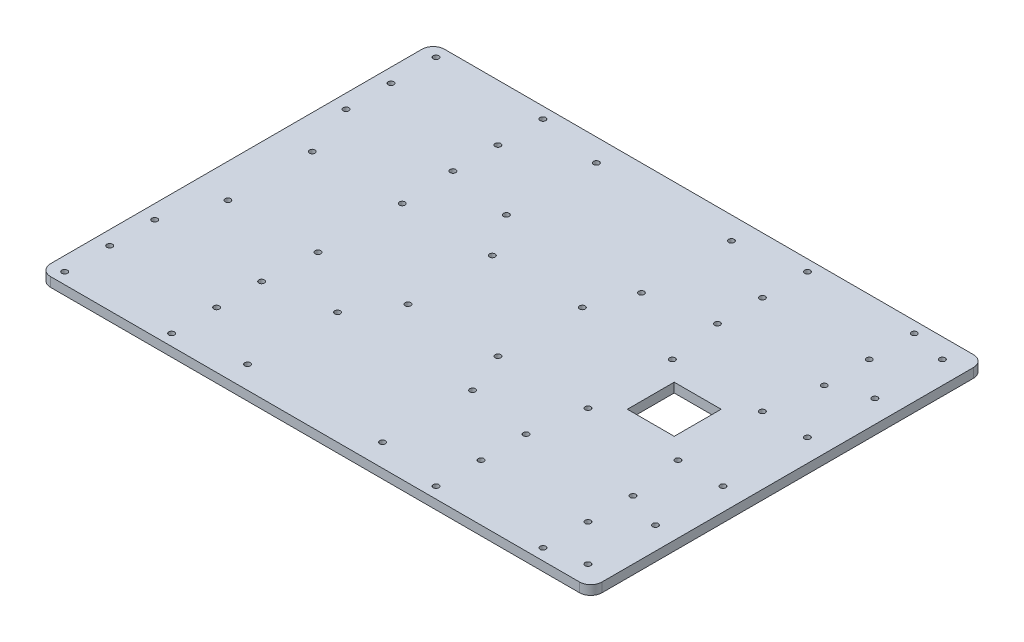
SolidWorks part; units mm, degrees
ref_plane "Front Plane" through (0, 0, 0) normal (0, 0, 1) x (1, 0, 0)
ref_plane "Top Plane" through (0, 0, 0) normal (0, 1, 0) x (1, 0, 0)
ref_plane "Right Plane" through (0, 0, 0) normal (1, 0, 0) x (0, 0, -1)
sketch "Sketch1" plane through (0, 0, 0) normal (0, 1, 0) x (1, 0, 0)
  line L0 (-127.5, 105) -> (-127.5, -105) construction
  line L1 (-129, -105) -> (129, -105)
  line L2 (-135, -99) -> (-135, 99)
  line L3 (-129, 105) -> (129, 105)
  line L4 (135, -99) -> (135, 99) construction
  line L5 (-135, -105) -> (135, 105) construction
  line L6 (-135, 105) -> (135, -105) construction
  line L8 (0, 105) -> (0, -105) construction
  line L9 (-135, 0) -> (135, 0) construction
  line L13 (129, 105) -> (153, 105)
  line L14 (159, 99) -> (159, -99)
  line L15 (153, -105) -> (129, -105)
  line L16 (147, 105) -> (147, -105) construction
  line L17 (159, -22.5) -> (-135, -22.5) construction
  line L19 (86, -12.5) -> (111, -12.5)
  line L20 (86, -12.5) -> (86, 12.5)
  line L21 (86, 12.5) -> (111, 12.5)
  line L22 (111, -12.5) -> (111, 12.5)
  line L23 (86, -12.5) -> (111, 12.5) construction
  line L24 (86, 12.5) -> (111, -12.5) construction
  line L25 (-36, -93) -> (36, -93) construction
  line L26 (-36, -93) -> (-36, -45) construction
  line L27 (-36, -45) -> (36, -45) construction
  line L28 (36, -93) -> (36, -45) construction
  line L29 (-36, -93) -> (36, -45) construction
  line L30 (-36, -45) -> (36, -93) construction
  circle A0 centre (-127.5, 99) radius 1.5
  circle A1 centre (-127.5, 75) radius 1.5
  circle A2 centre (-127.5, 51) radius 1.5
  circle A3 centre (-70.5, 99) radius 1.5
  circle A4 centre (-70.5, 75) radius 1.5
  circle A5 centre (-70.5, 51) radius 1.5
  circle A6 centre (70.5, 51) radius 1.5
  circle A7 centre (70.5, 75) radius 1.5
  circle A8 centre (70.5, 99) radius 1.5
  circle A9 centre (127.5, 51) radius 1.5
  circle A10 centre (127.5, 75) radius 1.5
  circle A11 centre (127.5, 99) radius 1.5
  circle A12 centre (127.5, -99) radius 1.5
  circle A13 centre (127.5, -75) radius 1.5
  circle A14 centre (127.5, -51) radius 1.5
  circle A15 centre (70.5, -99) radius 1.5
  circle A16 centre (70.5, -75) radius 1.5
  circle A17 centre (70.5, -51) radius 1.5
  circle A18 centre (-70.5, -51) radius 1.5
  circle A19 centre (-70.5, -75) radius 1.5
  circle A20 centre (-70.5, -99) radius 1.5
  circle A21 centre (-127.5, -51) radius 1.5
  circle A22 centre (-127.5, -75) radius 1.5
  circle A23 centre (-127.5, -99) radius 1.5
  arc A37 (129, 105) -> (135, 99) centre (129, 99) cw construction
  arc A38 (135, -99) -> (129, -105) centre (129, -99) cw construction
  arc A39 (-129, -105) -> (-135, -99) centre (-129, -99) cw
  arc A40 (-135, 99) -> (-129, 105) centre (-129, 99) cw
  arc A43 (153, -105) -> (159, -99) centre (153, -99) ccw
  arc A44 (159, 99) -> (153, 105) centre (153, 99) ccw
  circle A45 centre (147, -94.5) radius 1.5
  circle A46 centre (147, -58.5) radius 1.5
  circle A47 centre (147, -22.5) radius 1.5
  circle A51 centre (123, -22.5) radius 1.5
  circle A52 centre (75, -22.5) radius 1.5
  circle A53 centre (27, -22.5) radius 1.5
  circle A54 centre (-21, -22.5) radius 1.5
  circle A55 centre (-69, -22.5) radius 1.5
  circle A56 centre (-117, -22.5) radius 1.5
  circle A57 centre (-36, -93) radius 1.5
  circle A58 centre (36, -93) radius 1.5
  circle A59 centre (36, -45) radius 1.5
  circle A60 centre (-36, -45) radius 1.5
  circle A61 centre (123, 22.5) radius 1.5
  circle A62 centre (75, 22.5) radius 1.5
  circle A63 centre (27, 22.5) radius 1.5
  circle A64 centre (-21, 22.5) radius 1.5
  circle A65 centre (-69, 22.5) radius 1.5
  circle A66 centre (-117, 22.5) radius 1.5
  circle A67 centre (36, 93) radius 1.5
  circle A68 centre (36, 45) radius 1.5
  circle A69 centre (-36, 45) radius 1.5
  circle A70 centre (-36, 93) radius 1.5
  circle A71 centre (147, 94.5) radius 1.5
  circle A72 centre (147, 58.5) radius 1.5
  circle A73 centre (147, 22.5) radius 1.5
  point P0 (0, 0)
  point P59 (0, 0)
  point P72 (98.5, 0)
  point P78 (147, -22.5)
  point P79 (0, 0)
  point P80 (147, -22.5)
  point P88 (0, 0)
  point P93 (0, -69)
  point P98 (0, 0)
  dimension "D5" = 3
  dimension "D9" = 22.5
  dimension "D10" = 24
  dimension "D11" = 6
  dimension "D14" = 57
  dimension "D15" = 3
  dimension "D17" = 36
  dimension "D18" = 25
  dimension "D19" = 6
  dimension "D12" = 3
  dimension "D21" = 3
  dimension "D23" = 24
  dimension "D24" = 48
  dimension "D25" = 3
  dimension "D1" = 270
  dimension "D2" = 210
  dimension "D3" = 7.5
  dimension "D4" = 3
  dimension "D6" = 6
  dimension "D8" = 12
  dimension "D13" = 24
  dimension "D20" = 48
  dimension "D26" = 12
  dimension "D27" = 48
  dimension "D28" = 72
  dimension "D7" = 2
  dimension "D22" = 6
extrude "Boss-Extrude1" add sketch "Sketch1" along normal blind 5
